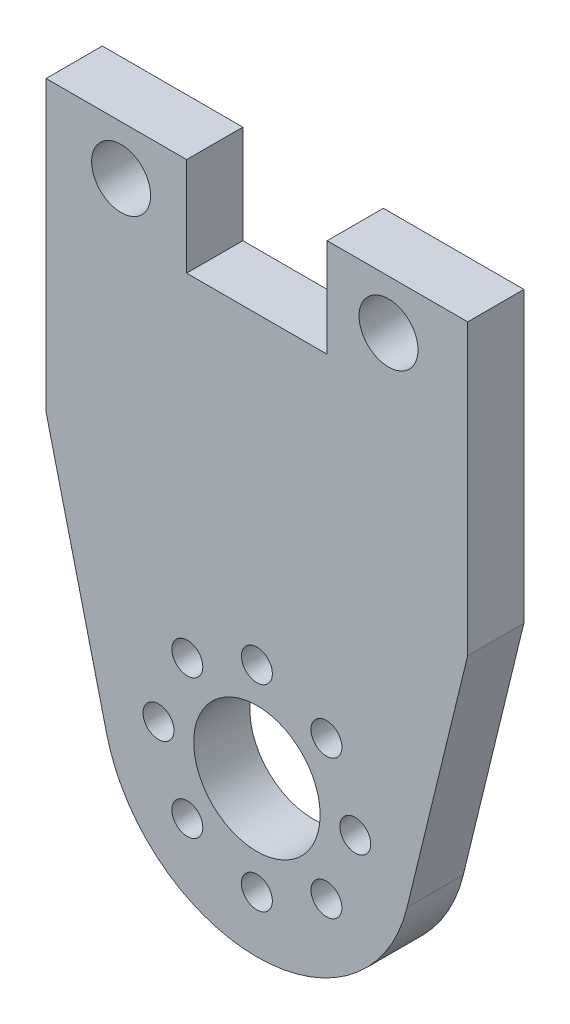
SolidWorks part; units mm, degrees
ref_plane "Plan de face" through (0, 0, 0) normal (0, 0, 1) x (1, 0, 0)
ref_plane "Plan de dessus" through (0, 0, 0) normal (0, 1, 0) x (1, 0, 0)
ref_plane "Plan de droite" through (0, 0, 0) normal (1, 0, 0) x (0, 0, -1)
sketch "Esquisse1" plane through (0, 0, 0) normal (0, 0, 1) x (1, 0, 0)
  line L0 (-15, 3) -> (-15, 7)
  line L1 (-15, 7) -> (-5, 7)
  line L2 (-5, 7) -> (-5, 0)
  line L3 (-5, 0) -> (5, 0)
  line L4 (5, 0) -> (5, 7)
  line L5 (5, 7) -> (15, 7)
  line L6 (15, 7) -> (15, 3)
  line L7 (-15, 3) -> (-15, -13.5741)
  line L8 (15, 3) -> (15, -13.5741)
  line L9 (0, 9.0284) -> (0, -50.6802) construction
  line L16 (-15, -13.5741) -> (-10.6864, -31.2508)
  line L18 (0, -28.643) -> (-11, -28.643) construction
  line L22 (15, -13.5741) -> (10.6864, -31.2508)
  circle A20 centre (0, -28.643) radius 4.5
  circle A21 centre (0, -21.643) radius 1.1
  circle A22 centre (0, -28.643) radius 4.5
  circle A23 centre (4.9497, -23.6933) radius 1.1
  circle A24 centre (0, -28.643) radius 4.5
  circle A25 centre (7, -28.643) radius 1.1
  circle A26 centre (0, -28.643) radius 4.5
  circle A27 centre (4.9497, -33.5928) radius 1.1
  circle A28 centre (0, -28.643) radius 4.5
  circle A29 centre (0, -35.643) radius 1.1
  circle A30 centre (0, -28.643) radius 4.5
  circle A31 centre (-4.9497, -33.5928) radius 1.1
  circle A32 centre (0, -28.643) radius 4.5
  circle A33 centre (-7, -28.643) radius 1.1
  circle A34 centre (0, -28.643) radius 4.5
  circle A35 centre (-4.9497, -23.6933) radius 1.1
  arc A39 (-10.6864, -31.2508) -> (10.6864, -31.2508) centre (0, -28.643) ccw
  point P2 (0, 0)
  dimension "D7" = 11
  dimension "D12" = 9
  dimension "D13" = 2.2
  dimension "D1" = 30
  dimension "D2" = 4
  dimension "D3" = 4
  dimension "D4" = 10
  dimension "D5" = 7
  dimension "D6" = 7
  dimension "D10" = 8
  dimension "D14" = 7
extrude "Boss.-Extru.1" add sketch "Esquisse1" along normal blind 4 contours L9 L3 L2 L1 L0 L7 A27 A31 A28 | L3 L9 A27 L8 L6 L5 L4 A23 A24 region at (0, -13.6112, 0)
sketch "Sketch1" plane through (0, 0, 0) normal (0, 0, -1) x (-1, 0, 0)
  circle A0 centre (-9.368, 3.5) radius 2.1
  circle A1 centre (9.6636, 3.5) radius 2.1
extrude "Cut-Extrude1" cut sketch "Sketch1" against normal through all
